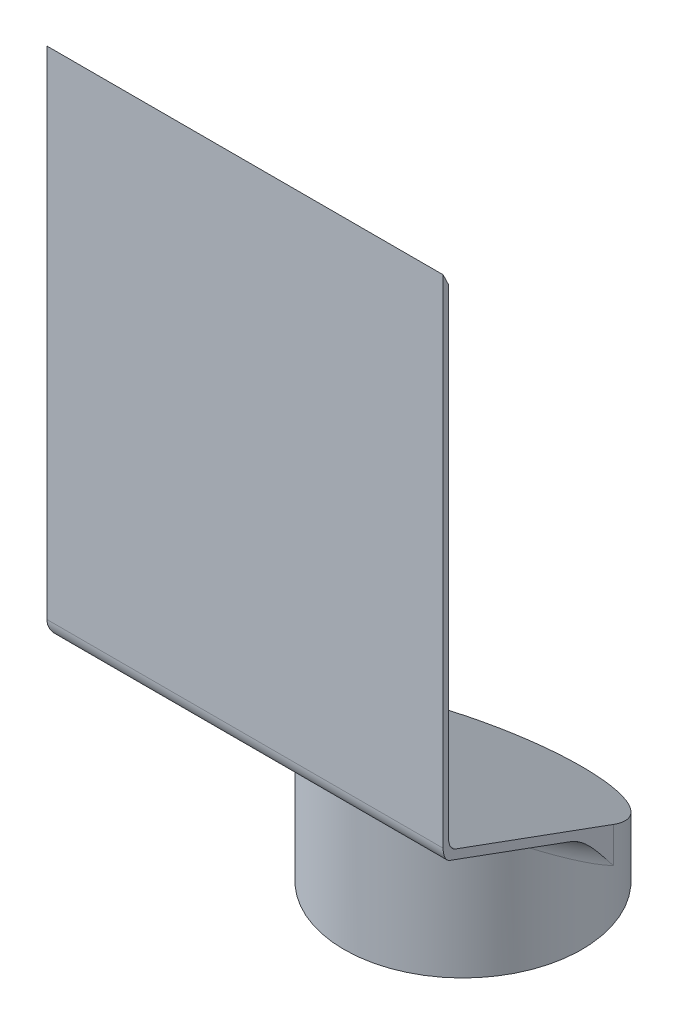
SolidWorks part; units mm, degrees
ref_plane "Front Plane" through (0, 0, 0) normal (0, 0, 1) x (1, 0, 0)
ref_plane "Top Plane" through (0, 0, 0) normal (0, 1, 0) x (1, 0, 0)
ref_plane "Right Plane" through (0, 0, 0) normal (1, 0, 0) x (0, 0, -1)
sketch "Sketch1" plane through (0, 0, 0) normal (0, 1, 0) x (1, 0, 0)
  circle A0 centre (0, 0) radius 30
  dimension "D1" = 60
extrude "Boss-Extrude2" add sketch "Sketch1" along normal blind 10
sketch "Sketch4" plane through (0, 10, 0) normal (0, 1, 0) x (1, 0, 0)
  line L4 (-50, -55) -> (50, -55)
  line L6 (-50, -55) -> (-28.4547, 9.5043)
  line L7 (50, -55) -> (28.4547, 9.5043)
  circle A0 centre (0, 0) radius 30 construction
  arc A1 (28.4547, 9.5043) -> (-28.4547, 9.5043) centre (0, 0) ccw
  point P2 (0, -30)
  point P4 (0, -55)
  dimension "D1" = 25
extrude "Boss-Extrude4" add sketch "Sketch4" along normal blind 175
sketch "Sketch8" plane through (0, 0, 0) normal (1, 0, 0) x (0, 0, -1)
  line L0 (-53, 181.5359) -> (-53, 57.9201)
  line L1 (-55, 185) -> (9.5043, 185) construction
  line L2 (-53, 57.9201) -> (30, 10)
  line L3 (30, 10) -> (30, 185)
  line L4 (30, 185) -> (-53, 185)
  line L5 (-30, 10) -> (9.5043, 10) construction
  line L6 (-55, 185) -> (-55, 10) construction
  line L7 (-55, 56.7654) -> (-30, 42.3316)
  line L8 (-30, 10) -> (-30, 42.3316)
  line L9 (-55, 56.7654) -> (-55, 10)
  line L10 (-55, 10) -> (-30, 10)
  line L11 (30, 0) -> (30, 185) construction
  line L12 (-55, 185) -> (-53, 181.5359)
  line L14 (-55, 185) -> (-53, 185)
  line L15 (55, 0) -> (-55, 0) construction
  dimension "D1" = 2
  dimension "D2" = 2
  dimension "D3" = 60
  dimension "D4" = 30
  dimension "D5" = 57.9201
extrude "Cut-Extrude3" cut sketch "Sketch8" against normal mid plane 100
sketch "Sketch10" plane through (0, 10, 0) normal (0, -1, 0) x (1, 0, 0)
  line L0 (41.6497, 30) -> (28.4547, -9.5043) construction
  line L1 (-28.4547, -9.5043) -> (-41.6497, 30) construction
  line L2 (41.6497, 30) -> (28.4547, -9.5043)
  line L3 (-28.4547, -9.5043) -> (-41.6497, 30)
  line L4 (-41.6497, 30) -> (-3.3184, 39.6585)
  line L5 (-3.3184, 39.6585) -> (41.6497, 30)
  circle A0 centre (0, 0) radius 30 construction
  arc A1 (28.4547, -9.5043) -> (-28.4547, -9.5043) centre (0, 0) ccw
extrude "Cut-Extrude4" cut sketch "Sketch10" against normal up to surface (37.908 mm away) up to face at (0, 49.5485, 42.5)
fillet "Fillet1" radius 5 3 edges at (0, 42.3316, 30) (0, 56.7654, 55) (0, 57.9201, 53)
